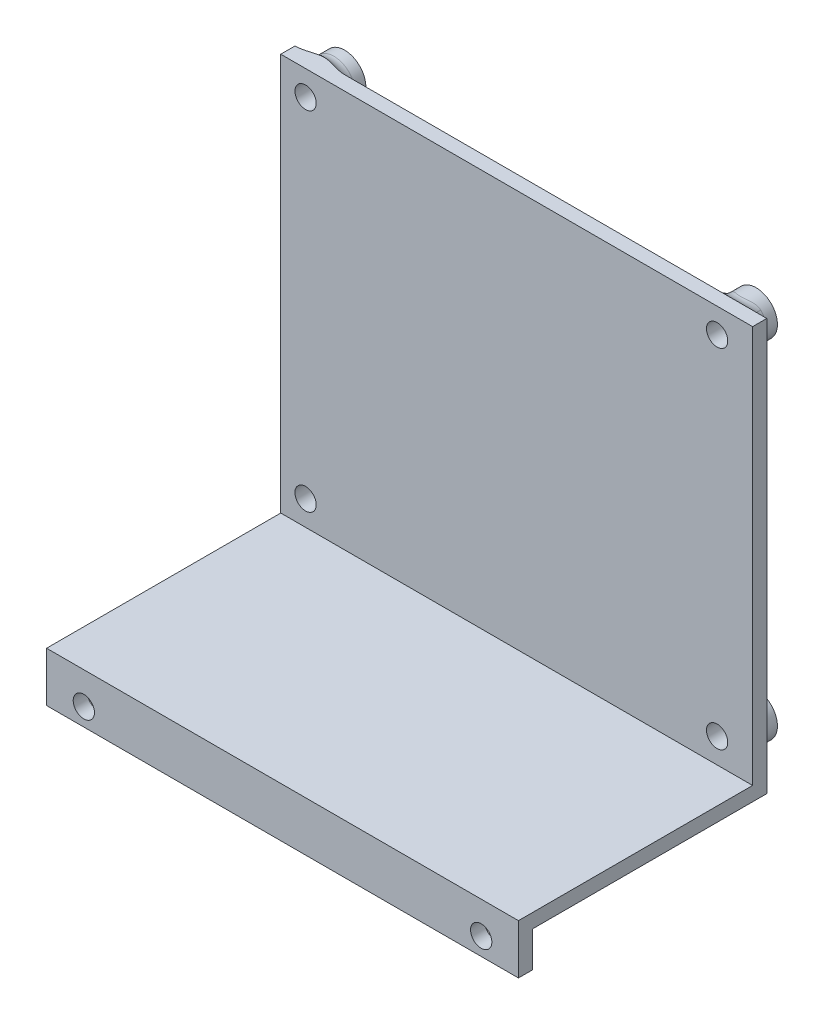
SolidWorks part; units mm, degrees
ref_plane "Piano frontale" through (0, 0, 0) normal (0, 0, 1) x (1, 0, 0)
ref_plane "Piano superiore" through (0, 0, 0) normal (0, 1, 0) x (1, 0, 0)
ref_plane "Piano destro" through (0, 0, 0) normal (1, 0, 0) x (0, 0, -1)
sketch "Schizzo1" plane through (0, 0, 0) normal (0, 0, 1) x (1, 0, 0)
  line L1 (87, 28) -> (-87, 28)
  line L2 (87, 28) -> (87, -28)
  line L3 (87, -28) -> (-87, -28)
  line L4 (-87, 28) -> (-87, -28)
  line L5 (87, 28) -> (-87, -28) construction
  line L6 (87, -28) -> (-87, 28) construction
  point P0 (0, 0)
  dimension "D1" = 56
  dimension "D2" = 174
extrude "Estrusione-Estrusione1" add sketch "Schizzo1" along normal blind 2
sketch "Schizzo4" plane through (0, 0, 0) normal (0, 0, -1) x (-1, 0, 0)
  line L0 (87, 0) -> (-87, 0) construction
  line L1 (87, 28) -> (87, -28) construction
  line L2 (-87, -28) -> (-87, 28) construction
  line L3 (83.5, 0) -> (83.5, -24.5) construction
  line L4 (83.5, -24.5) -> (25.5, -24.5) construction
  line L5 (83.5, 0) -> (83.5, 24.5) construction
  line L6 (83.5, 24.5) -> (25.5, 24.5) construction
  line L7 (25.5, 24.5) -> (25.5, -24.5) construction
  circle A0 centre (83.5, -24.5) radius 1.5
  circle A1 centre (25.5, -24.5) radius 1.5
  circle A2 centre (25.5, 24.5) radius 1.5
  circle A3 centre (83.5, 24.5) radius 1.5
  circle A4 centre (83.5, -24.5) radius 3
  circle A5 centre (25.5, -24.5) radius 3
  circle A6 centre (25.5, 24.5) radius 3
  circle A7 centre (83.5, 24.5) radius 3
  dimension "D5" = 3
  dimension "D6" = 3
  dimension "D7" = 3
  dimension "D8" = 3
  dimension "D9" = 6
  dimension "D10" = 6
  dimension "D11" = 6
  dimension "D12" = 6
  dimension "D1" = 3.5
  dimension "D2" = 24.5
  dimension "D3" = 58
  dimension "D4" = 24.5
extrude "Estrusione-Estrusione4" add sketch "Schizzo4" along normal blind 3.5
sketch "Schizzo5" plane through (0, 0, 0) normal (0, 0, -1) x (-1, 0, 0)
  circle A0 centre (83.5, -24.5) radius 1.5
  circle A1 centre (25.5, -24.5) radius 1.5
  circle A2 centre (25.5, 24.5) radius 1.5
  circle A3 centre (83.5, 24.5) radius 1.5
extrude "Taglio-Estrusione1" cut sketch "Schizzo5" against normal blind 2
sketch "Schizzo6" plane through (0, 0, 0) normal (0, 0, -1) x (-1, 0, 0)
  line L0 (-87, 0) -> (0, 0) construction
  line L1 (-87, -28) -> (-87, 28) construction
  line L2 (-87, -24.1216) -> (-87, 24.1216)
  line L3 (-87, -24.1216) -> (-31.6596, -24.1216) construction
  line L4 (-87, 24.1216) -> (-30.39, 24.1216) construction
  line L5 (-87, 19.0416) -> (-82.46, 19.0416) construction
  line L6 (-87, -8.8984) -> (-82.46, -8.8984) construction
  circle A0 centre (-30.39, 24.1216) radius 1.5
  circle A1 centre (-31.6596, -24.1216) radius 1.5
  circle A2 centre (-82.46, -8.8984) radius 1.5
  circle A3 centre (-82.46, 19.0416) radius 1.5
  circle A4 centre (-30.39, 24.1216) radius 3
  circle A5 centre (-31.6596, -24.1216) radius 3
  circle A6 centre (-82.46, 19.0416) radius 3
  circle A7 centre (-82.46, -8.8984) radius 3
  point P8 (-87, 0)
  dimension "D9" = 3
  dimension "D10" = 3
  dimension "D11" = 3
  dimension "D12" = 3
  dimension "D13" = 6
  dimension "D14" = 6
  dimension "D15" = 6
  dimension "D16" = 6
  dimension "D1" = 48.2433
  dimension "D2" = 0
  dimension "D3" = 55.3404
  dimension "D4" = 56.61
  dimension "D5" = 4.54
  dimension "D6" = 4.54
  dimension "D7" = 15.2233
  dimension "D8" = 5.08
extrude "Estrusione-Estrusione5" add sketch "Schizzo6" along normal blind 3.5 contours A7 | A2 | A6 | A3 | A4 | A0 | A5 | A1
sketch "Schizzo7" plane through (0, 0, 0) normal (0, 0, -1) x (-1, 0, 0)
  circle A0 centre (-82.46, 19.0416) radius 1.5
  circle A1 centre (-30.39, 24.1216) radius 1.5
  circle A2 centre (-31.6596, -24.1216) radius 1.5
  circle A3 centre (-82.46, -8.8984) radius 1.5
extrude "Taglio-Estrusione2" cut sketch "Schizzo7" against normal blind 2
fillet "Raccordo1" radius 2 6 edges at (-86.5, 24.5, 0) (-28.5, 24.5, 0) (27.39, 24.1216, 0) (28.6596, -24.1216, 0) (79.46, -8.8984, 0) (79.46, 19.0416, 0)
sketch "Schizzo8" plane through (0, 0, 0) normal (0, 0, -1) x (-1, 0, 0)
  line L0 (20.5, -24.5) -> (20.5, -28) construction
  line L1 (87, -28) -> (-28.5039, -28) construction
  line L2 (20.5, -28) -> (20.5, 28)
  line L3 (-27.2343, 28) -> (21.9293, 28) construction
  line L4 (20.5, -28) -> (-87, -28)
  line L5 (-87, -28) -> (-87, 28)
  line L6 (-87, 28) -> (20.5, 28)
  arc A0 (29.0707, -28) -> (21.9293, -28) centre (25.5, -24.5) ccw construction
extrude "Taglio-Estrusione3" cut sketch "Schizzo8" against normal blind 10
sketch "Schizzo9" plane through (0, 0, 0) normal (0, 0, -1) x (-1, 0, 0)
  line L0 (87, -28) -> (20.5, -28)
  line L1 (20.5, -28) -> (20.5, -30)
  line L2 (20.5, -30) -> (87, -30)
  line L3 (87, -30) -> (87, -28)
  dimension "D1" = 2
extrude "Estrusione-Estrusione6" add sketch "Schizzo9" against normal blind 35
fillet "Raccordo2" radius 2 2 edges at (-28.5, -24.5, 0) (-86.5, -24.5, 0)
sketch "Schizzo10" plane through (0, -30, 0) normal (0, -1, 0) x (1, 0, 0)
  line L0 (-87, 35) -> (-87, 0) construction
  line L1 (-20.5, 35) -> (-87, 35)
  line L2 (-20.5, 35) -> (-20.5, 33)
  line L3 (-20.5, 33) -> (-87, 33)
  line L4 (-87, 35) -> (-87, 33)
  dimension "D1" = 2
extrude "Estrusione-Estrusione7" add sketch "Schizzo10" along normal blind 5
sketch "Schizzo11" plane through (0, 0, 33) normal (0, 0, -1) x (-1, 0, 0)
  line L0 (20.5, -32.5) -> (87, -32.5) construction
  line L1 (20.5, -35) -> (20.5, -30) construction
  line L2 (87, -35) -> (87, -30) construction
  line L3 (53.75, -32.5) -> (53.75, -35) construction
  line L4 (87, -35) -> (20.5, -35) construction
  circle A0 centre (25.75, -32.5) radius 1.5
  circle A1 centre (81.75, -32.5) radius 1.5
  dimension "D1" = 3
  dimension "D2" = 28
extrude "Taglio-Estrusione4" cut sketch "Schizzo11" against normal blind 5
